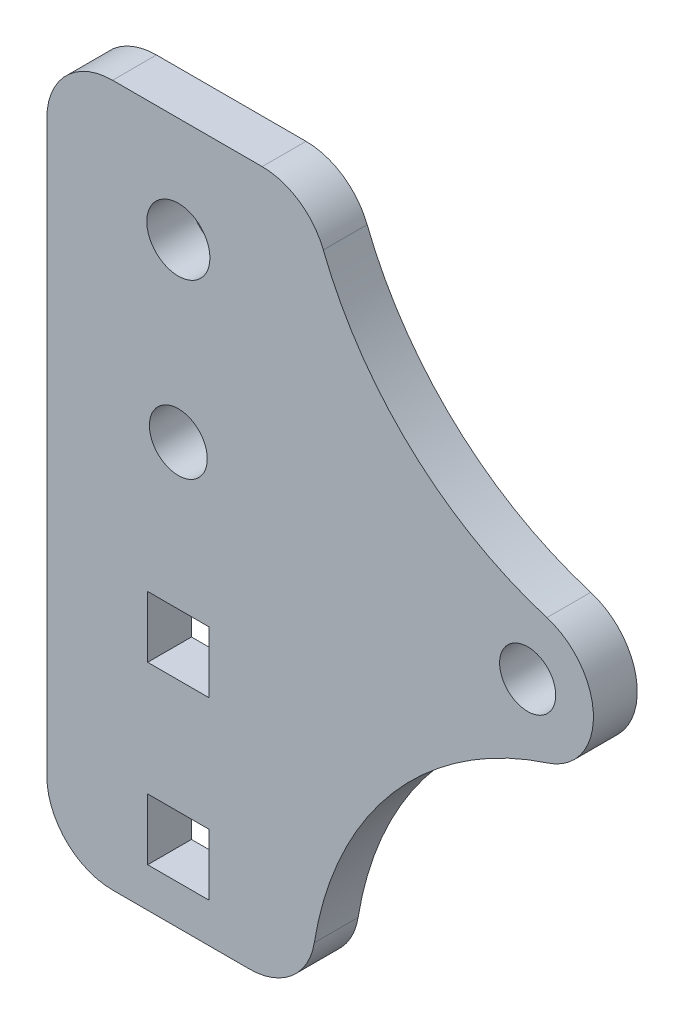
SolidWorks part; units mm, degrees
ref_plane "Front Plane" through (0, 0, 0) normal (0, 0, 1) x (1, 0, 0)
ref_plane "Top Plane" through (0, 0, 0) normal (0, 1, 0) x (1, 0, 0)
ref_plane "Right Plane" through (0, 0, 0) normal (1, 0, 0) x (0, 0, -1)
sketch "Sketch1" plane through (0, 0, 0) normal (0, 0, 1) x (1, 0, 0)
  line L0 (0, 0) -> (0, -25.4) construction
  line L1 (9.525, -30.48) -> (9.525, -33.0089) construction
  line L2 (0, 0) -> (25.3033, -2.2138) construction
  line L6 (-9.525, -30.48) -> (-9.525, 20.32)
  line L13 (-9.525, 20.32) -> (9.525, 20.32)
  line L15 (-2.2225, -27.6225) -> (2.2225, -27.6225)
  line L16 (-2.2225, -27.6225) -> (-2.2225, -23.1775)
  line L17 (-2.2225, -23.1775) -> (2.2225, -23.1775)
  line L18 (2.2225, -27.6225) -> (2.2225, -23.1775)
  line L19 (-2.2225, -27.6225) -> (2.2225, -23.1775) construction
  line L20 (-2.2225, -23.1775) -> (2.2225, -27.6225) construction
  line L21 (0, 12.7) -> (25.3033, -2.2138) construction
  line L22 (-9.525, -30.48) -> (9.525, -30.48)
  line L24 (-2.2225, -14.9225) -> (2.2225, -14.9225)
  line L25 (-2.2225, -14.9225) -> (-2.2225, -10.4775)
  line L26 (-2.2225, -10.4775) -> (2.2225, -10.4775)
  line L27 (2.2225, -14.9225) -> (2.2225, -10.4775)
  line L28 (-2.2225, -14.9225) -> (2.2225, -10.4775) construction
  line L29 (-2.2225, -10.4775) -> (2.2225, -14.9225) construction
  circle A2 centre (25.3033, -2.2138) radius 2.032
  arc A5 (26.7742, -6.7434) -> (26.6969, 2.3403) centre (25.3033, -2.2138) ccw
  circle A9 centre (0, 12.7) radius 2.286
  circle A10 centre (0, 0) radius 2.0955
  arc A13 (9.525, 20.32) -> (26.6969, 2.3403) centre (34.1291, 26.6286) ccw
  arc A14 (9.525, -30.48) -> (26.7742, -6.7434) centre (34.4815, -30.48) cw
  point P16 (0, -30.48)
  point P29 (0, -12.7)
  dimension "D2" = 4.191
  dimension "D6" = 5.08
  dimension "D7" = 12.7
  dimension "D8" = 4.572
  dimension "D10" = 4.064
  dimension "D11" = 25.4
  dimension "D3" = 4.7625
  dimension "D1" = 25.4
  dimension "D4" = 25.4
  dimension "D5" = 85
  dimension "D9" = 4.445
  dimension "D12" = 19.05
  dimension "D13" = 7.62
extrude "Boss-Extrude1" add sketch "Sketch1" along normal blind 3.175
fillet "Fillet1" radius 4.7625 4 edges at (-9.525, -30.48, 1.5875) (9.525, 20.32, 1.5875) (-9.525, 20.32, 1.5875) (9.525, -30.48, 1.5875)
ref_plane "Plane1" through (0, -25.4, 0) normal (0, 1, 0) x (1, 0, 0)
ref_axis "Axis1" through (0, -25.4, -0.1588) along (0, 0, 1)
